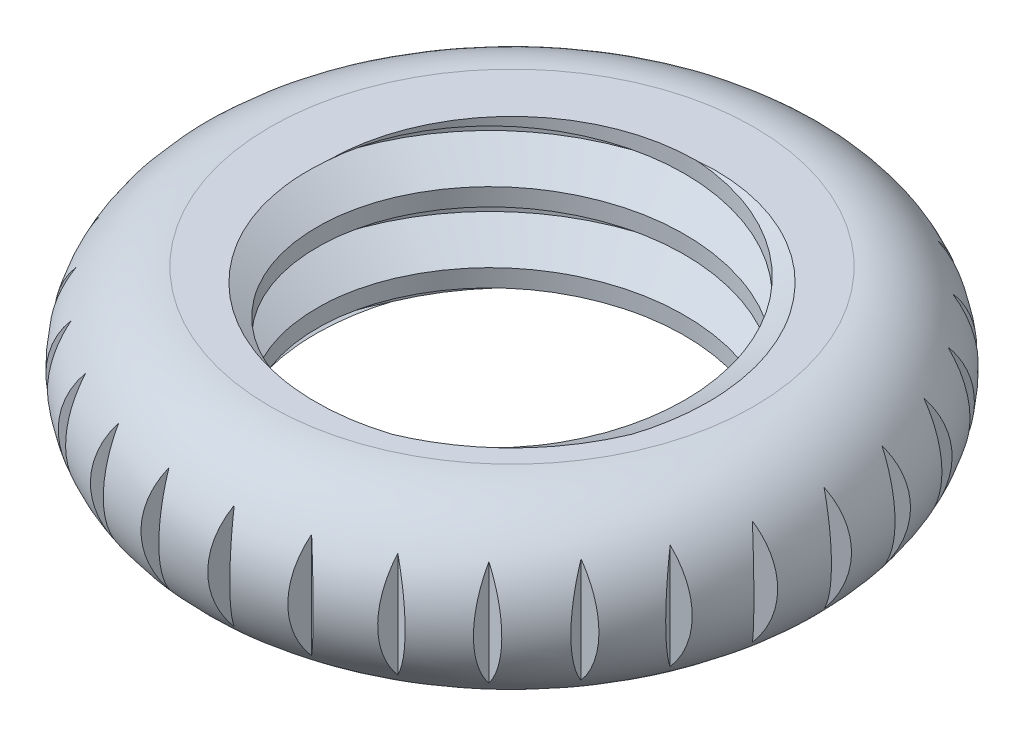
SolidWorks part; units mm, degrees
ref_plane "Alzado" through (0, 0, 0) normal (0, 0, 1) x (1, 0, 0)
ref_plane "Planta" through (0, 0, 0) normal (0, 1, 0) x (1, 0, 0)
ref_plane "Vista lateral" through (0, 0, 0) normal (1, 0, 0) x (0, 0, -1)
sketch "Croquis1" plane through (0, 0, 0) normal (0, 1, 0) x (1, 0, 0)
  circle A0 centre (0, 0) radius 9.4
  dimension "D1" = 18.8
extrude "Saliente-Extruir1" add sketch "Croquis1" along normal blind 5
fillet "Redondeo3" 2 edges at (0, 0, 9.4) (0, 5, 9.4) type full round first side face at (0, 0, 9.4) second side face at (0, 5, 9.4) middle face at (0, 5, 9.4)
sketch "Croquis5" plane through (0, 5, 0) normal (0, 1, 0) x (1, 0, 0)
  line L2 (-8.9, 0) -> (-9.65, 0.433)
  line L3 (-9.65, 0.433) -> (-9.65, -0.433)
  line L4 (-9.65, -0.433) -> (-8.9, 0)
  circle A0 centre (0, 0) radius 9.4 construction
  circle A1 centre (-9.4, 0) radius 0.25 construction
  dimension "D1" = 0.5
extrude "Cortar-Extruir3" cut sketch "Croquis5" against normal blind 5
pattern_circular "MatrizC1" count 30 over 360 about axis through (0, 5, 0) along (0, 1, 0) of "Cortar-Extruir3"
sketch "Croquis11" plane through (0, 5, 0) normal (0, 1, 0) x (1, 0, 0)
  circle A0 centre (0, 0) radius 5.25
  dimension "D1" = 10.5
extrude "Cortar-Extruir5" cut sketch "Croquis11" against normal blind 55
thread "Rosca4" pitch 2 method cut profile "Perfil de rosca4" start angle 0, offset 2, length 24, pitch 2, diameter 10.5
ref_plane "Plano4" through (-5.25, 7, 0) normal (0, 0, 1) x (-1, 0, 0)
sketch "Perfil de rosca4" plane through (-5.25, 7, 0) normal (0, 0, 1) x (-1, 0, 0)
  line L0 (0, 0) -> (0, 2) construction
  line L1 (0, 0) -> (1.0825, 0.625)
  line L2 (1.0825, 0.625) -> (1.0825, 0.875)
  line L3 (1.0825, 0.875) -> (0, 1.5)
  line L4 (1.0825, 0.75) -> (0, 0.75) construction
  line L11 (0, 0) -> (0, 1.5)
  point P2 (0, 0)
  dimension "Pitch" = 2
  dimension "Profile_Angle" = 60
  dimension "Profile_Land" = 0.25
  dimension "Profile_Height" = 1.0825
